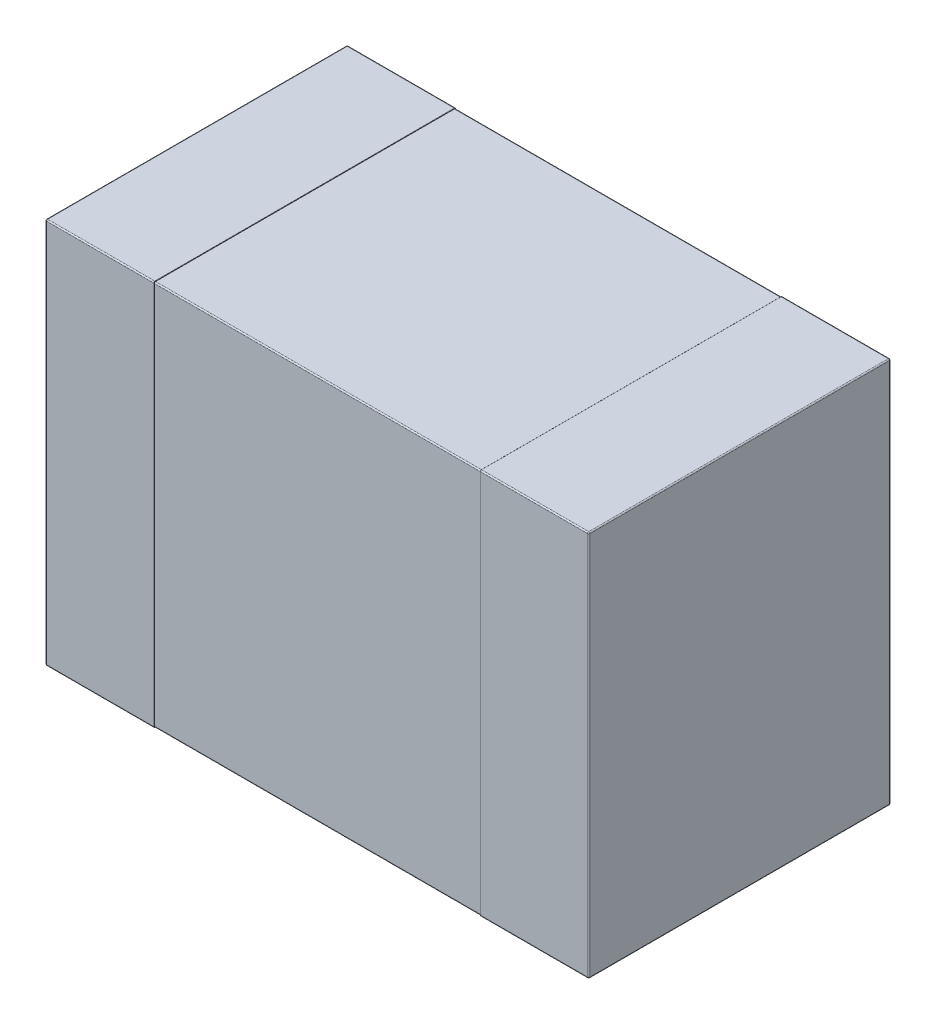
SolidWorks part; units mm, degrees
ref_plane "Top Plane" through (0, 0, 0) normal (0, 0, 1) x (1, 0, 0)
ref_plane "Front Plane" through (0, 0, 0) normal (0, 1, 0) x (1, 0, 0)
ref_plane "Side Plane" through (0, 0, 0) normal (1, 0, 0) x (0, 0, -1)
sketch "Sketch1" plane through (0, 0, 0) normal (0, 0, 1) x (1, 0, 0)
  line L1 (-2.25, 1.6) -> (2.25, 1.6)
  line L2 (-2.25, 1.6) -> (-2.25, -1.6)
  line L3 (-2.25, -1.6) -> (2.25, -1.6)
  line L4 (2.25, 1.6) -> (2.25, -1.6)
  dimension "D1" = 4.5
  dimension "D2" = 2.25
  dimension "D3" = 3.2
  dimension "D4" = 1.6
extrude "All body" add sketch "Sketch1" along normal blind 2.5
sketch "Sketch2" plane through (0, 0, 0) normal (1, 0, 0) x (0, 0, -1)
  line L14 (-0.003, 1.597) -> (-2.497, 1.597)
  line L15 (-0.003, -1.597) -> (-0.003, 1.597)
  line L16 (-2.497, -1.597) -> (-0.003, -1.597)
  line L17 (-2.497, 1.597) -> (-2.497, -1.597)
  line L18 (-0.003, 1.597) -> (-2.497, 1.597)
  line L19 (-0.003, -1.597) -> (-0.003, 1.597)
  line L20 (-2.497, -1.597) -> (-0.003, -1.597)
  line L21 (-2.497, 1.597) -> (-2.497, -1.597)
  dimension "D1" = 0.003
extrude "Cut out the body for pin" cut sketch "Sketch2" against normal blind 1.35 and the other way blind 1.35 flip side to cut
fillet "Body fillet" radius 0.01 4 edges at (0, 1.597, 0.003) (0, 1.597, 2.497) (0, -1.597, 0.003) (0, -1.597, 2.497)
fillet "Pin fillet a" radius 0.01 16 edges at (2.25, -1.6, 1.25) (2.25, 0, 2.5) (2.25, 1.6, 1.25) (2.25, 0, 0) (-2.25, 1.6, 1.25) (-2.25, 0, 2.5) (-2.25, -1.6, 1.25) (-2.25, 0, 0) (1.8, 1.6, 2.5) (1.8, -1.6, 2.5) (1.8, -1.6, 0) (1.8, 1.6, 0) (-1.8, 1.6, 0) (-1.8, -1.6, 0) (-1.8, 1.6, 2.5) (-1.8, -1.6, 2.5)
fillet "Pin fillet b" radius 0.003 16 edges at (1.35, -1.5971, 2.4971) (1.35, -1.6, 1.25) (1.35, -1.5971, 0.0029) (1.35, 0, 0) (1.35, 1.5971, 0.0029) (1.35, 1.6, 1.25) (1.35, 1.5971, 2.4971) (-1.35, -1.5971, 2.4971) (-1.35, -1.6, 1.25) (-1.35, -1.5971, 0.0029) (-1.35, 0, 0) (-1.35, 1.5971, 0.0029) (-1.35, 1.6, 1.25) (-1.35, 1.5971, 2.4971) (1.35, 0, 2.5) (-1.35, 0, 2.5)
